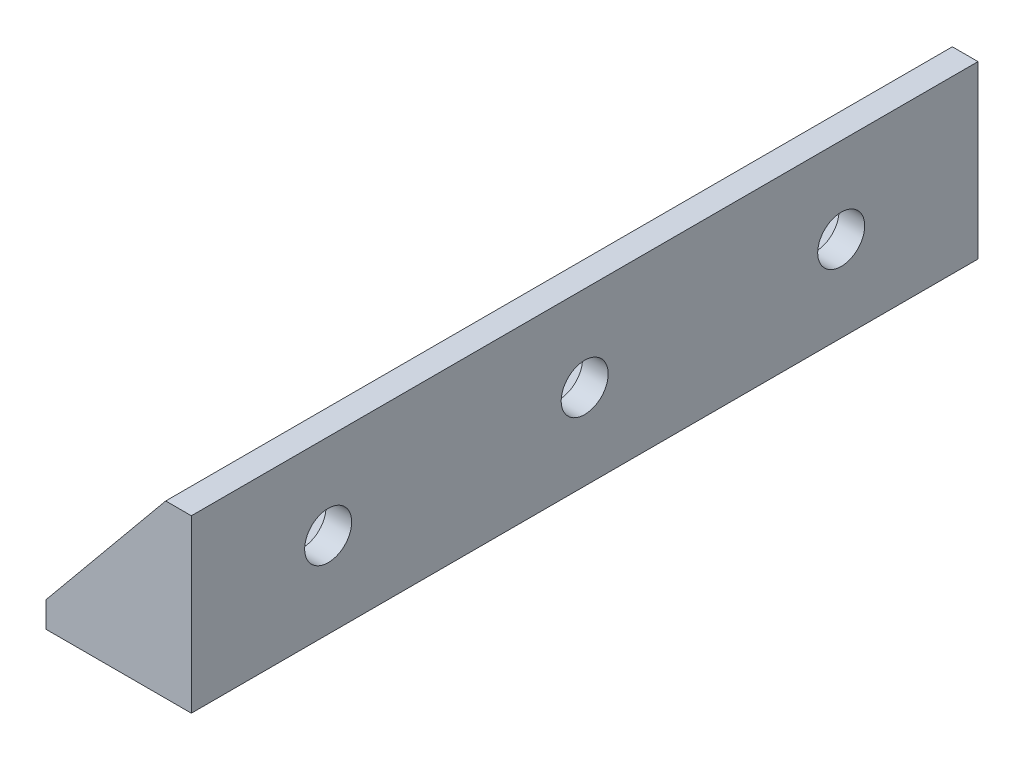
SolidWorks part; units mm, degrees
ref_plane "Front Plane" through (0, 0, 0) normal (0, 0, 1) x (1, 0, 0)
ref_plane "Top Plane" through (0, 0, 0) normal (0, 1, 0) x (1, 0, 0)
ref_plane "Right Plane" through (0, 0, 0) normal (1, 0, 0) x (0, 0, -1)
sketch "Sketch1" plane through (0, 0, 0) normal (0, 1, 0) x (1, 0, 0)
  line L1 (-7, 40) -> (7, 40)
  line L2 (-7, 40) -> (-7, -40)
  line L3 (-7, -40) -> (7, -40)
  line L4 (10, 40) -> (10, -40)
  line L5 (-7, -40) -> (7, -40)
  line L6 (-7, -40) -> (-7, -46)
  line L7 (-7, -46) -> (10, -46)
  line L8 (10, -40) -> (10, -46)
  line L9 (-7, 40) -> (7, 40)
  line L10 (-7, 40) -> (-7, 46)
  line L11 (-7, 46) -> (10, 46)
  line L12 (10, 40) -> (10, 46)
  line L13 (-7, -11) -> (7, -11)
  line L14 (-7, -11) -> (-7, -19)
  line L15 (-7, -19) -> (7, -19)
  line L16 (10, -12) -> (10, -18)
  line L17 (7, 11) -> (7, -11)
  line L18 (-7, 19) -> (7, 19)
  line L19 (-7, 19) -> (-7, 11)
  line L20 (-7, 11) -> (7, 11)
  line L21 (10, 18) -> (10, 12)
  line L22 (7, 46) -> (10, 46)
  line L23 (7, 40) -> (7, 19)
  line L24 (7, -46) -> (10, -46)
  line L25 (10, 46) -> (10, -46)
  line L26 (7, -19) -> (7, -40)
  line L27 (10, -46) -> (50, -46)
  line L28 (10, -46) -> (10, 46)
  line L29 (10, 46) -> (50, 46)
  line L30 (50, -46) -> (50, 46)
  circle A0 centre (0, -30) radius 2.5
  circle A1 centre (0, 0) radius 2.5
  circle A2 centre (0, 30) radius 2.5
  point P7 (0, -40)
  point P12 (-7, 0)
  dimension "D3" = 5
  dimension "D1" = 30
  dimension "D2" = 30
  dimension "D4" = 10
  dimension "D5" = 10
  dimension "D6" = 6
  dimension "D7" = 11
  dimension "D8" = 11
  dimension "D9" = 11
  dimension "D10" = 11
  dimension "D11" = 3
  dimension "D12" = 40
extrude "Boss-Extrude1" add sketch "Sketch1" along normal blind 3 contours L15 L26 L3 L6 L7 L8 L4 L12 L11 L10 L1 L23 L18 L2 L20 L17 L13 | L26 L15 L2 L3 A0 | L20 L2 L13 L17 A1 | L23 L1 L2 L18 A2 region at (-6.0644, 0, -43) region at (0, 0, -39.7476) region at (0, 0, -10.7392) region at (0, 0, 19.2524)
extrude "Boss-Extrude6" add sketch "Sketch1<3>" along normal blind 20 contours L15 L26 L3 L6 L7 L8 L4 L12 L11 L10 L1 L23 L18 L2 L20 L17 L13 region at (-6.0644, 0, -43)
sketch "Sketch1<3>" plane through (0, 0, 0) normal (0, 1, 0) x (1, 0, 0) same geometry as "Sketch1"
sketch "Sketch3" plane through (0, 0, 46) normal (0, 0, 1) x (1, 0, 0)
  line L0 (-7, 3) -> (7, 20)
  line L1 (-7, 20) -> (-7, 0) construction
  line L2 (-7, 20) -> (10, 20) construction
  line M4 (10, 20) -> (-7, 20)
  line M5 (-7, 20) -> (-7, 0)
extrude "Cut-Extrude2" cut sketch "Sketch3" against normal through all and the other way through all contours L0 M5 M4 region at (-2.3333, 14.3333, 46)
sketch "Sketch2" plane through (7, 0, 0) normal (-1, 0, 0) x (0, 0, 1)
  line L3 (-40, 0) -> (40, 0) construction
  circle A0 centre (-30, 10) radius 2.75
  circle A1 centre (0, 10) radius 2.75
  circle A2 centre (30, 10) radius 2.75
  dimension "D1" = 5.5
  dimension "D2" = 10
extrude "Cut-Extrude1" cut sketch "Sketch2" against normal blind 5
